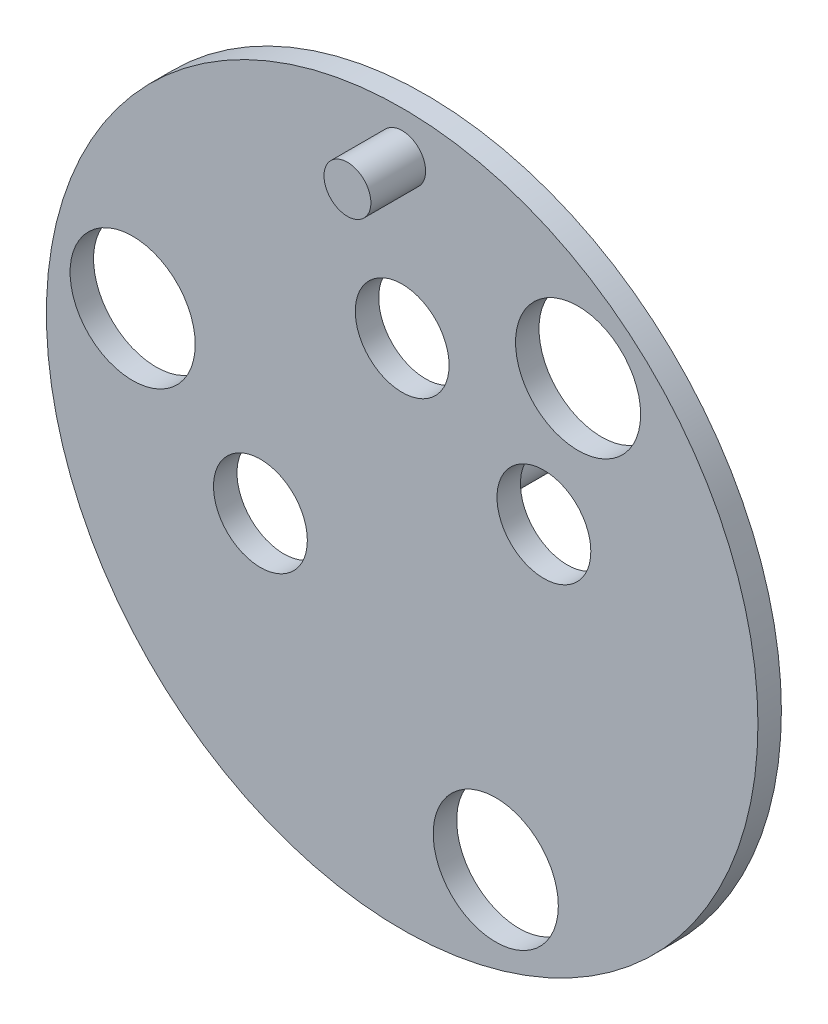
SolidWorks part; units mm, degrees
ref_plane "Front Plane" through (0, 0, 0) normal (0, 0, 1) x (1, 0, 0)
ref_plane "Top Plane" through (0, 0, 0) normal (0, 1, 0) x (1, 0, 0)
ref_plane "Right Plane" through (0, 0, 0) normal (1, 0, 0) x (0, 0, -1)
other "Center of Mass"
sketch "Sketch1" plane through (0, 0, 0) normal (0, 0, 1) x (1, 0, 0)
  circle A0 centre (0, 0) radius 227.5
  circle A1 centre (0, 200) radius 15
  dimension "D2" = 30
  dimension "D3" = 455
  dimension "D1" = 200
extrude "Boss-Extrude1" add sketch "Sketch1" along normal mid plane 15 contours A0
extrude "Boss-Extrude2" add sketch "Sketch1<3>" along normal up to surface (35 mm away) from surface contours A1 region at (0, 200, 0) starting at face at (227.5, 0, 7.5)
sketch "Sketch1<3>" plane through (0, 0, 0) normal (0, 0, 1) x (1, 0, 0) same geometry as "Sketch1"
sketch "Sketch2" plane through (0, 0, 7.5) normal (0, 0, 1) x (1, 0, 0)
  line L0 (90.6308, 42.2618) -> (-90.6308, -42.2618) construction
  line L1 (0, -100) -> (0, 100) construction
  line L2 (-172.3414, 30.3884) -> (0, 0) construction
  line L3 (59.8535, -164.4462) -> (0, 0) construction
  line L4 (0, 0) -> (112.4878, 134.0578) construction
  circle A0 centre (-172.3414, 30.3884) radius 40
  circle A2 centre (0, 100) radius 30
  circle A4 centre (90.6308, 42.2618) radius 30
  circle A9 centre (-90.6308, -42.2618) radius 30
  circle A10 centre (112.4878, 134.0578) radius 40
  circle A11 centre (59.8535, -164.4462) radius 40
  dimension "D1" = 60
  dimension "D4" = 100
  dimension "D8" = 60
  dimension "D11" = 3
  dimension "D12" = 120
  dimension "D7" = 80
  dimension "D2" = 100
  dimension "D6" = 175
  dimension "D3" = 100
  dimension "D9" = 115
  dimension "D10" = 80
  dimension "D13" = 120
extrude "Cut-Extrude1" cut sketch "Sketch2" against normal through all
sketch "Sketch3" plane through (0, 0, 0) normal (0, 0, 1) x (1, 0, 0)
  circle A0 centre (0, 0) radius 15
  dimension "D1" = 30
extrude "Boss-Extrude3" add sketch "Sketch3" against normal blind 74.828 from surface contours A0 starting at face at (-132.3414, 30.3884, -7.5)
